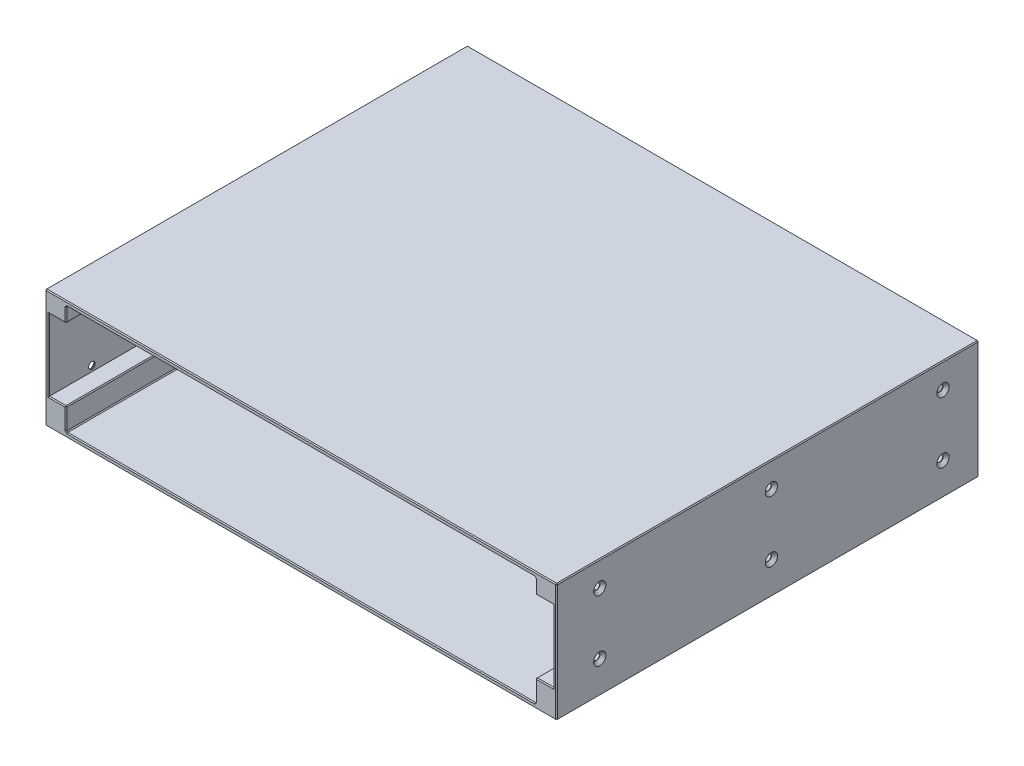
SolidWorks part; units mm, degrees
ref_plane "Front" through (0, 0, 0) normal (0, 0, 1) x (1, 0, 0)
ref_plane "Top" through (0, 0, 0) normal (0, 1, 0) x (1, 0, 0)
ref_plane "Right" through (0, 0, 0) normal (1, 0, 0) x (0, 0, -1)
sketch "Sketch1" plane through (0, 0, 0) normal (0, 0, 1) x (1, 0, 0)
  line L1 (-138, -30) -> (138, -30)
  line L2 (-138, -30) -> (-138, 30)
  line L3 (-138, 30) -> (138, 30)
  line L4 (138, -30) -> (138, 30)
  line L5 (-138, -30) -> (138, 30) construction
  line L6 (-138, 30) -> (138, -30) construction
  point P0 (0, 0)
  dimension "D1" = 276
  dimension "D2" = 60
extrude "Walls" add sketch "Sketch1" along normal blind 230 thin thin type one direction wall 2.5
sketch "Sketch2" plane through (0, 0, 0) normal (0, 0, 1) x (1, 0, 0)
  line L12 (140.5, -32.5) -> (140.5, 32.5)
  line L13 (140.5, 32.5) -> (-140.5, 32.5)
  line L14 (-140.5, 32.5) -> (-140.5, -32.5)
  line L15 (-140.5, -32.5) -> (140.5, -32.5)
  line L16 (140.5, -32.5) -> (140.5, 32.5)
  line L17 (140.5, 32.5) -> (-140.5, 32.5)
  line L18 (-140.5, 32.5) -> (-140.5, -32.5)
  line L19 (-140.5, -32.5) -> (140.5, -32.5)
  dimension "D1" = 0
extrude "Back Plate" add sketch "Sketch2" against normal blind 2
sketch "Sketch7" plane through (138.5, 0, 0) normal (1, 0, 0) x (0, 0, -1)
  line L0 (0, -30) -> (0, 30) construction
  line L1 (0, -17.75) -> (-230, -17.75)
  line L2 (0, -17.75) -> (0, 21.75)
  line L3 (0, 21.75) -> (-230, 21.75)
  line L4 (-230, -17.75) -> (-230, 21.75)
  line L5 (-230, -32.5) -> (-230, 32.5) construction
extrude "Drawer Slide Pocket" cut sketch "Sketch7" against normal up to next
sketch "Sketch8" plane through (138, 0, 0) normal (-1, 0, 0) x (0, 0, 1)
  line L0 (230, 32.5) -> (230, -32.5) construction
  line L1 (0, -30) -> (230, -30)
  line L2 (0, -30) -> (0, -17.75)
  line L3 (0, -17.75) -> (230, -17.75)
  line L4 (230, -30) -> (230, -17.75)
  line L6 (0, 30) -> (230, 30)
  line L7 (0, 30) -> (0, 21.75)
  line L8 (0, 21.75) -> (230, 21.75)
  line L9 (230, 30) -> (230, 21.75)
extrude "Drawer Slide Brackets" add sketch "Sketch8" along normal blind 9
sketch "Sketch9" plane through (140.5, 0, 0) normal (1, 0, 0) x (0, 0, -1)
  point P0 (-206.2857, -14.75)
  point P1 (-206.2857, 18.75)
  point P3 (-112, -14.75)
  point P5 (-112, 18.75)
  point P7 (-17.7143, -14.75)
  point P9 (-17.7143, 18.75)
hole_wizard "CSK for M3 SFHCS1" positions "Sketch9" profile "Sketch10" countersink size "M3" standard "ANSI Metric" end condition up to next
sketch "Sketch10" plane through (140.5, -14.75, 206.2857) normal (0, 1, 0) x (0, 0, -1)
  line L0 (0, 0) -> (0, 2)
  line L1 (0, 2) -> (1.8, 2)
  line L2 (1.7, 1.9) -> (1.7, 1.66)
  line L3 (1.7, 1.66) -> (3.36, 0)
  line L5 (3.36, 0) -> (0, 0)
  line L6 (-1.7, 1.66) -> (-3.36, 0) construction
  line L7 (1.8, 2) -> (1.7, 1.9)
  line L8 (-1.8, 2) -> (-1.7, 1.9) construction
  line L11 (0, -6.35) -> (0, 107.95) construction
  dimension "Thru Hole Dia." = 3.4
  dimension "Thru Hole Depth" = 2
  dimension "Near C'Sink Dia." = 6.72
  dimension "Near C'Sink Angle" = 90
  dimension "Far C'Sink Dia." = 3.6
  dimension "Far C'Sink Angle" = 90
mirror "Drawer Slide Pocket mirror" about plane through (0, 0, 0) normal (1, 0, 0) of "CSK for M3 SFHCS1", "Drawer Slide Pocket", "Drawer Slide Brackets"
sketch "Sketch3" plane through (0, -32.5, 0) normal (0, 1, 0) x (1, 0, 0)
  line L0 (0, 2) -> (0, -114) construction
  line L1 (-114.5192, -23.9808) -> (114.5192, -23.9808) construction
  line L2 (-114.5192, -23.9808) -> (-114.5192, -204.0192) construction
  line L3 (-114.5192, -204.0192) -> (114.5192, -204.0192) construction
  line L4 (114.5192, -23.9808) -> (114.5192, -204.0192) construction
  line L5 (-114.5192, -23.9808) -> (114.5192, -204.0192) construction
  line L6 (-114.5192, -204.0192) -> (114.5192, -23.9808) construction
  line L8 (0, -114) -> (0, -230) construction
  line L10 (-140.5, -23.9808) -> (-114.5192, -23.9808) construction
  line L11 (140.5, 2) -> (-140.5, 2) construction
  line L12 (-114.5192, -23.9808) -> (-114.5192, 2) construction
  line L13 (-57.2596, -23.9808) -> (-57.2596, -15.3205) construction
  line L14 (-114.5192, -32.641) -> (-107.0192, -28.3109)
  line L15 (-107.0192, -28.3109) -> (-107.0192, -19.6506)
  line L16 (-107.0192, -19.6506) -> (-114.5192, -15.3205)
  line L17 (-114.5192, -15.3205) -> (-122.0192, -19.6506)
  line L18 (-122.0192, -19.6506) -> (-122.0192, -28.3109)
  line L19 (-122.0192, -28.3109) -> (-114.5192, -32.641)
  line L20 (-57.2596, -15.3205) -> (-57.2596, -6.6603) construction
  line L21 (0, -114) -> (114.5192, -114) construction
  line L22 (122.0192, -28.3109) -> (114.5192, -32.641)
  line L23 (122.0192, -19.6506) -> (122.0192, -28.3109)
  line L24 (114.5192, -15.3205) -> (122.0192, -19.6506)
  line L25 (107.0192, -19.6506) -> (114.5192, -15.3205)
  line L26 (107.0192, -28.3109) -> (107.0192, -19.6506)
  line L27 (114.5192, -32.641) -> (107.0192, -28.3109)
  line L28 (122.0192, -208.3494) -> (122.0192, -199.6891)
  line L29 (114.5192, -212.6795) -> (122.0192, -208.3494)
  line L30 (107.0192, -208.3494) -> (114.5192, -212.6795)
  line L31 (107.0192, -199.6891) -> (107.0192, -208.3494)
  line L32 (114.5192, -195.359) -> (107.0192, -199.6891)
  line L33 (122.0192, -199.6891) -> (114.5192, -195.359)
  line L34 (-122.0192, -199.6891) -> (-114.5192, -195.359)
  line L35 (-122.0192, -208.3494) -> (-122.0192, -199.6891)
  line L36 (-114.5192, -212.6795) -> (-122.0192, -208.3494)
  line L37 (-107.0192, -208.3494) -> (-114.5192, -212.6795)
  line L38 (-107.0192, -199.6891) -> (-107.0192, -208.3494)
  line L39 (-114.5192, -195.359) -> (-107.0192, -199.6891)
  line L40 (-57.2596, -6.6603) -> (-57.2596, 2) construction
  line L41 (-114.5192, -10.9904) -> (-57.2596, -10.9904) construction
  line L42 (-57.2596, -10.9904) -> (0, -10.9904) construction
  line L43 (-140.5, -230) -> (-140.5, 2) construction
  line L44 (140.5, -230) -> (-140.5, -230) construction
  circle A0 centre (-114.5192, -23.9808) radius 7.5 construction
  point P0 (0, -114)
  dimension "D1" = 15
extrude "Foot Pocket" cut sketch "Sketch3" along normal blind 1.5 draft 45
sketch "Sketch4" plane through (0, 32.5, 0) normal (0, -1, 0) x (1, 0, 0)
  line L20 (-107.2192, 208.2339) -> (-114.5192, 212.4486)
  line L21 (-114.5192, 212.4486) -> (-121.8192, 208.2339)
  line L22 (-121.8192, 208.2339) -> (-121.8192, 199.8046)
  line L23 (-121.8192, 199.8046) -> (-114.5192, 195.5899)
  line L24 (-114.5192, 195.5899) -> (-107.2192, 199.8046)
  line L25 (-107.2192, 199.8046) -> (-107.2192, 208.2339)
  line L26 (-107.2192, 208.2339) -> (-114.5192, 212.4486)
  line L27 (-114.5192, 212.4486) -> (-121.8192, 208.2339)
  line L28 (-121.8192, 208.2339) -> (-121.8192, 199.8046)
  line L29 (-121.8192, 199.8046) -> (-114.5192, 195.5899)
  line L30 (-114.5192, 195.5899) -> (-107.2192, 199.8046)
  line L31 (-107.2192, 199.8046) -> (-107.2192, 208.2339)
  line L38 (-114.5192, 32.4101) -> (-121.8192, 28.1954)
  line L39 (-121.8192, 28.1954) -> (-121.8192, 19.7661)
  line L40 (-121.8192, 19.7661) -> (-114.5192, 15.5514)
  line L41 (-114.5192, 15.5514) -> (-107.2192, 19.7661)
  line L42 (-107.2192, 19.7661) -> (-107.2192, 28.1954)
  line L43 (-107.2192, 28.1954) -> (-114.5192, 32.4101)
  line L44 (-114.5192, 32.4101) -> (-121.8192, 28.1954)
  line L45 (-121.8192, 28.1954) -> (-121.8192, 19.7661)
  line L46 (-121.8192, 19.7661) -> (-114.5192, 15.5514)
  line L47 (-114.5192, 15.5514) -> (-107.2192, 19.7661)
  line L48 (-107.2192, 19.7661) -> (-107.2192, 28.1954)
  line L49 (-107.2192, 28.1954) -> (-114.5192, 32.4101)
  line L56 (114.5192, 212.4486) -> (107.2192, 208.2339)
  line L57 (107.2192, 208.2339) -> (107.2192, 199.8046)
  line L58 (107.2192, 199.8046) -> (114.5192, 195.5899)
  line L59 (114.5192, 195.5899) -> (121.8192, 199.8046)
  line L60 (121.8192, 199.8046) -> (121.8192, 208.2339)
  line L61 (121.8192, 208.2339) -> (114.5192, 212.4486)
  line L62 (114.5192, 212.4486) -> (107.2192, 208.2339)
  line L63 (107.2192, 208.2339) -> (107.2192, 199.8046)
  line L64 (107.2192, 199.8046) -> (114.5192, 195.5899)
  line L65 (114.5192, 195.5899) -> (121.8192, 199.8046)
  line L66 (121.8192, 199.8046) -> (121.8192, 208.2339)
  line L67 (121.8192, 208.2339) -> (114.5192, 212.4486)
  line L74 (121.8192, 19.7661) -> (121.8192, 28.1954)
  line L75 (114.5192, 15.5514) -> (121.8192, 19.7661)
  line L76 (107.2192, 19.7661) -> (114.5192, 15.5514)
  line L77 (107.2192, 28.1954) -> (107.2192, 19.7661)
  line L78 (114.5192, 32.4101) -> (107.2192, 28.1954)
  line L79 (121.8192, 28.1954) -> (114.5192, 32.4101)
  line L80 (121.8192, 19.7661) -> (121.8192, 28.1954)
  line L81 (114.5192, 15.5514) -> (121.8192, 19.7661)
  line L82 (107.2192, 19.7661) -> (114.5192, 15.5514)
  line L83 (107.2192, 28.1954) -> (107.2192, 19.7661)
  line L84 (114.5192, 32.4101) -> (107.2192, 28.1954)
  line L85 (121.8192, 28.1954) -> (114.5192, 32.4101)
  dimension "D1" = 0.2
  dimension "D2" = 0.2
  dimension "D3" = 0.2
  dimension "D4" = 0.2
extrude "Feet" [suppressed] add sketch "Sketch4" against normal blind 1.3 draft 45
chamfer "Deburs 1" distance 0.5 angle 45 34 edges at (-138.5, 2, 230) (-133.75, -17.75, 230) (-129, -17.75, 115) (-129, -23.875, 230) (0, -30, 230) (0, 30, 230) (-133.75, 21.75, 230) (-129, 21.75, 115) (-129, 25.875, 230) (-129, 30, 115) (0, 30, 0) (129, 30, 115) (129, 25.875, 230) (129, 21.75, 115) (133.75, 21.75, 230) (138.5, 2, 230) (133.75, -17.75, 230) (129, -17.75, 115) (129, -23.875, 230) (-129, -30, 115) (0, -30, 0) (129, -30, 115) (140.5, 0, 230) (0, -32.5, 230) (-140.5, 0, 230) (0, 32.5, 230) (-140.5, 0, -2) (-140.5, 32.5, 114) (0, 32.5, -2) (140.5, 32.5, 114) (140.5, 0, -2) (140.5, -32.5, 114) (0, -32.5, -2) (-140.5, -32.5, 114)
chamfer "Deburs 2" distance 0.5 angle 45 4 edges at (129, -23.875, 0) (129, 25.875, 0) (-129, 25.875, 0) (-129, -23.875, 0)
